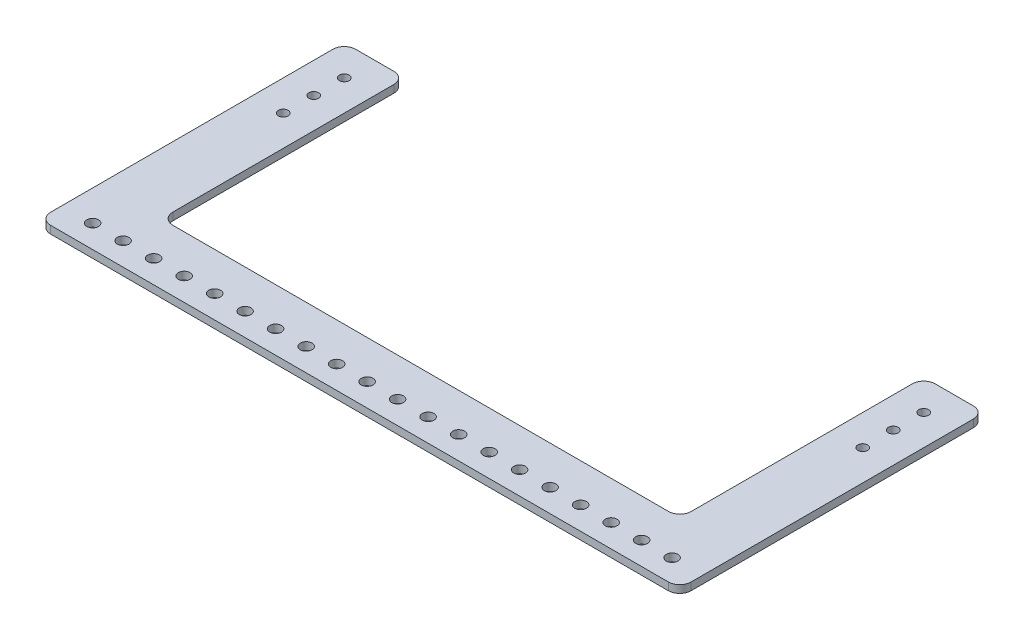
SolidWorks part; units mm, degrees
material "6061-T6 (SS)"
ref_plane "Front Plane" through (0, 0, 0) normal (0, 0, 1) x (1, 0, 0)
ref_plane "Top Plane" through (0, 0, 0) normal (0, 1, 0) x (1, 0, 0)
ref_plane "Right Plane" through (0, 0, 0) normal (1, 0, 0) x (0, 0, -1)
sketch "Sketch2" plane through (0, 0, 0) normal (0, 1, 0) x (1, 0, 0)
  line L0 (0, 63.5) -> (0, -63.5) construction
  line L1 (-133.35, -63.5) -> (133.35, -63.5)
  line L2 (-133.35, -63.5) -> (-133.35, 63.5)
  line L3 (-133.35, 63.5) -> (133.35, 63.5)
  line L4 (133.35, -63.5) -> (133.35, 63.5)
  line L5 (-133.35, -63.5) -> (133.35, 63.5) construction
  line L6 (-133.35, 63.5) -> (133.35, -63.5) construction
  line L7 (-107.95, 63.5) -> (107.95, 63.5)
  line L8 (-107.95, 63.5) -> (-107.95, -38.0365)
  line L9 (-107.95, -38.0365) -> (107.95, -38.0365)
  line L10 (107.95, 63.5) -> (107.95, -38.0365)
  line L11 (133.35, 63.5) -> (107.95, 63.5) construction
  line L12 (133.35, 63.5) -> (133.35, -38.0365) construction
  line L13 (133.35, -38.0365) -> (107.95, -38.0365) construction
  line L14 (107.95, 63.5) -> (107.95, -38.0365) construction
  circle A0 centre (-120.65, 50.8) radius 2.0193
  circle A1 centre (-120.65, 38.1) radius 2.0193
  circle A2 centre (-120.65, 25.4) radius 2.0193
  circle A6 centre (120.65, 25.4) radius 2.0193
  circle A7 centre (120.65, 38.1) radius 2.0193
  circle A8 centre (120.65, 50.8) radius 2.0193
  point P0 (0, 0)
  point P10 (0, -38.0365)
  point P11 (0, -63.5)
  dimension "D8" = 4.0386
  dimension "D1" = 266.7
  dimension "D2" = 127
  dimension "D3" = 215.9
  dimension "D4" = 25.4635
  dimension "D5" = 12.7
  dimension "D6" = 12.7
  dimension "D7" = 12.7
  dimension "D9" = 12.7
  dimension "D10" = 12.7
  dimension "D11" = 12.7
extrude "Boss-Extrude1" add sketch "Sketch2" along normal blind 3.175 contours L3 L10 L9 L8 L2 L1 L4 A7 A0 A1 A2 A6 A8 region at (-130.3961, 0, 0)
fillet "Fillet1" radius 4.7625 8 edges at (133.35, 1.5875, -63.5) (-133.35, 1.5875, 63.5) (-133.35, 1.5875, -63.5) (-107.95, 1.5875, -63.5) (-107.95, 1.5875, 38.0365) (107.95, 1.5875, 38.0365) (107.95, 1.5875, -63.5) (133.35, 1.5875, 63.5)
sketch "Sketch3" plane through (0, 3.175, 0) normal (0, 1, 0) x (1, 0, 0)
  line L0 (-133.35, -58.7375) -> (-133.35, 58.7375) construction
  line L1 (-128.5875, -63.5) -> (128.5875, -63.5) construction
  line L2 (0, -38.0365) -> (0, -63.5) construction
  line L3 (-103.1875, -38.0365) -> (103.1875, -38.0365) construction
  circle A0 centre (-120.65, -53.975) radius 2.4384
  circle A19 centre (-107.95, -53.975) radius 2.4384
  circle A20 centre (-95.25, -53.975) radius 2.4384
  circle A21 centre (-82.55, -53.975) radius 2.4384
  circle A22 centre (-69.85, -53.975) radius 2.4384
  circle A23 centre (-57.15, -53.975) radius 2.4384
  circle A24 centre (-44.45, -53.975) radius 2.4384
  circle A25 centre (-31.75, -53.975) radius 2.4384
  circle A26 centre (-19.05, -53.975) radius 2.4384
  circle A27 centre (-6.35, -53.975) radius 2.4384
  circle A28 centre (6.35, -53.975) radius 2.4384
  circle A29 centre (19.05, -53.975) radius 2.4384
  circle A30 centre (31.75, -53.975) radius 2.4384
  circle A31 centre (44.45, -53.975) radius 2.4384
  circle A32 centre (57.15, -53.975) radius 2.4384
  circle A33 centre (69.85, -53.975) radius 2.4384
  circle A34 centre (82.55, -53.975) radius 2.4384
  circle A35 centre (95.25, -53.975) radius 2.4384
  circle A36 centre (107.95, -53.975) radius 2.4384
  circle A37 centre (120.65, -53.975) radius 2.4384
  dimension "D1" = 4.8768
  dimension "D5" = 12.7
  dimension "D2" = 12.7
  dimension "D3" = 9.525
  dimension "D4" = 20
extrude "Cut-Extrude1" cut sketch "Sketch3" against normal through all
